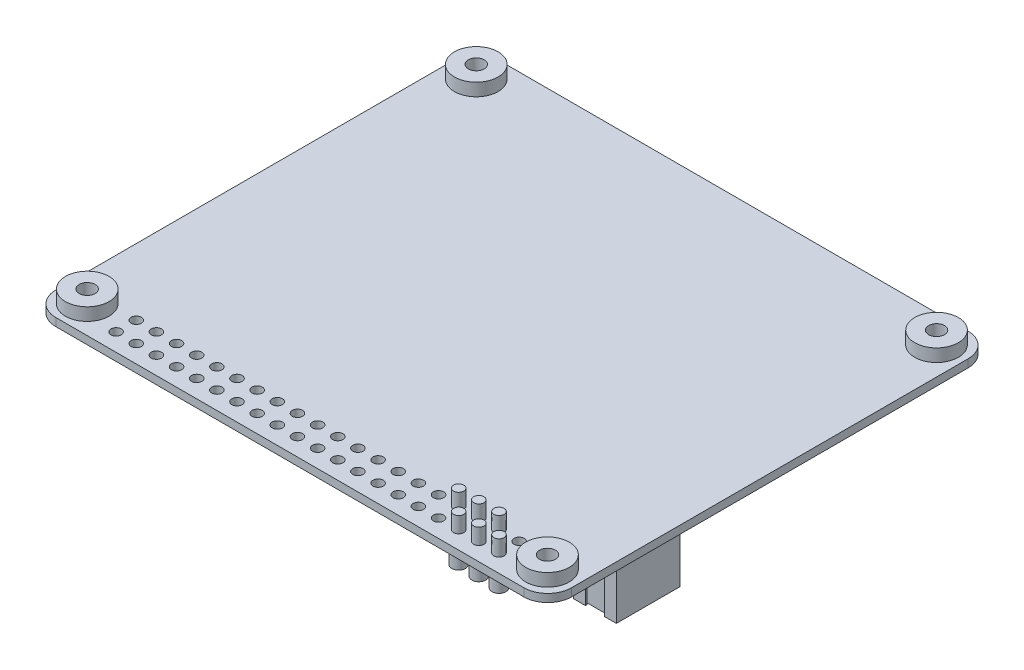
SolidWorks part; units mm, degrees
ref_plane "前视基准面" through (0, 0, 0) normal (0, 0, 1) x (1, 0, 0)
ref_plane "上视基准面" through (0, 0, 0) normal (0, 1, 0) x (1, 0, 0)
ref_plane "右视基准面" through (0, 0, 0) normal (1, 0, 0) x (0, 0, -1)
sketch "草图1" plane through (0, 0, 0) normal (0, 1, 0) x (1, 0, 0)
  line L1 (32.5, -28) -> (-32.5, -28)
  line L2 (32.5, -28) -> (32.5, 28)
  line L3 (32.5, 28) -> (-32.5, 28)
  line L4 (-32.5, -28) -> (-32.5, 28)
  line L5 (32.5, -28) -> (-32.5, 28) construction
  line L6 (32.5, 28) -> (-32.5, -28) construction
  point P0 (0, 0)
  dimension "D1" = 56
  dimension "D2" = 65
extrude "凸台-拉伸1" add sketch "草图1" along normal blind 1
fillet "圆角1" radius 3 4 edges at (32.5, 0.5, -28) (32.5, 0.5, 28) (-32.5, 0.5, 28) (-32.5, 0.5, -28)
sketch "草图2" plane through (0, 1, 0) normal (0, 1, 0) x (1, 0, 0)
  circle A0 centre (-29.0307, 24.5287) radius 2.75
  circle A1 centre (28.9808, 24.5287) radius 2.75
  circle A2 centre (-29.0307, -24.5065) radius 2.75
  circle A3 centre (28.9808, -24.5065) radius 2.75
  dimension "D1" = 5.5
extrude "凸台-拉伸2" add sketch "草图2" along normal blind 1.6
sketch "草图3" plane through (0, 2.6, 0) normal (0, 1, 0) x (1, 0, 0)
  circle A0 centre (-29.0307, 24.5287) radius 1
  circle A1 centre (28.9808, 24.5287) radius 1
  circle A2 centre (-29.0307, -24.5065) radius 1
  circle A3 centre (28.9808, -24.5065) radius 1
  dimension "D1" = 2
extrude "切除-拉伸1" cut sketch "草图3" against normal up to next
sketch "草图4" plane through (0, 0, 0) normal (0, -1, 0) x (1, 0, 0)
  line L0 (29.5, -28) -> (-29.5, -28) construction
  line L1 (25.5, -28) -> (16.5, -28)
  line L2 (25.5, -28) -> (25.5, -20.6)
  line L3 (25.5, -20.6) -> (16.5, -20.6)
  line L4 (16.5, -28) -> (16.5, -20.6)
  line L5 (32.5, 25) -> (32.5, -25) construction
  dimension "D1" = 7.4
  dimension "D2" = 9
  dimension "D3" = 7
extrude "凸台-拉伸3" add sketch "草图4" along normal blind 3.2
sketch "草图5" plane through (0, 0, -28) normal (0, 0, -1) x (-1, 0, 0)
  line L0 (-29.5, 0) -> (-25.5, 0) construction
  line L1 (-16.5, -3.2) -> (-25.5, -3.2)
  line L2 (-16.5, -3.2) -> (-16.5, 0)
  line L3 (-16.5, 0) -> (-25.5, 0)
  line L4 (-25.5, -3.2) -> (-25.5, 0)
  line L5 (-25.5, -3.2) -> (-25.5, 0) construction
extrude "凸台-拉伸4" add sketch "草图5" along normal blind 1
fillet "圆角3" radius 1 4 edges at (25.5, 0, -28.5) (25.5, -3.2, -24.8) (16.5, -3.2, -24.8) (16.5, 0, -28.5)
sketch "草图6" plane through (0, 0, 0) normal (0, -1, 0) x (1, 0, 0)
  line L0 (-32.5, -25) -> (-32.5, 25) construction
  circle A0 centre (-17.5, 0) radius 7
  dimension "D1" = 14
  dimension "D2" = 15
extrude "凸台-拉伸5" add sketch "草图6" along normal blind 2
sketch "草图8" plane through (0, 0, 0) normal (0, -1, 0) x (1, 0, 0)
  circle A0 centre (28.9808, 24.5065) radius 2
  circle A1 centre (28.9808, -24.5287) radius 2
  circle A2 centre (-29.0307, -24.5287) radius 2
  circle A3 centre (-29.0307, 24.5065) radius 2
  dimension "D1" = 4
extrude "凸台-拉伸6" add sketch "草图8" along normal blind 0.5
sketch "草图9" plane through (0, 0, 0) normal (0, 1, 0) x (1, 0, 0)
  circle A0 centre (-29.0307, 24.5287) radius 1
  circle A1 centre (28.9808, 24.5287) radius 1
  circle A2 centre (-29.0307, -24.5065) radius 1
  circle A3 centre (28.9808, -24.5065) radius 1
  circle A4 centre (28.9808, -24.5065) radius 2 construction
  circle A5 centre (28.9808, 24.5287) radius 2 construction
  circle A6 centre (-29.0307, -24.5065) radius 2 construction
  circle A7 centre (-29.0307, 24.5287) radius 2 construction
extrude "切除-拉伸2" cut sketch "草图9" against normal up to next
sketch "草图10" plane through (0, 0, -29) normal (0, 0, -1) x (-1, 0, 0)
  line L8 (-17.5, -0.2) -> (-24.5, -0.2)
  line L9 (-25.3, -1) -> (-25.3, -2.2)
  line L10 (-24.5, -3) -> (-17.5, -3)
  line L11 (-16.7, -2.2) -> (-16.7, -1)
  line L12 (-17.5, -0.2) -> (-24.5, -0.2)
  line L13 (-25.3, -1) -> (-25.3, -2.2)
  line L14 (-24.5, -3) -> (-17.5, -3)
  line L15 (-16.7, -2.2) -> (-16.7, -1)
  arc A8 (-24.5, -0.2) -> (-25.3, -1) centre (-24.5, -1) ccw
  arc A9 (-25.3, -2.2) -> (-24.5, -3) centre (-24.5, -2.2) ccw
  arc A10 (-17.5, -3) -> (-16.7, -2.2) centre (-17.5, -2.2) ccw
  arc A11 (-16.7, -1) -> (-17.5, -0.2) centre (-17.5, -1) ccw
  arc A12 (-24.5, -0.2) -> (-25.3, -1) centre (-24.5, -1) ccw
  arc A13 (-25.3, -2.2) -> (-24.5, -3) centre (-24.5, -2.2) ccw
  arc A14 (-17.5, -3) -> (-16.7, -2.2) centre (-17.5, -2.2) ccw
  arc A15 (-16.7, -1) -> (-17.5, -0.2) centre (-17.5, -1) ccw
  dimension "D1" = 0.2
extrude "切除-拉伸3" cut sketch "草图10" against normal blind 8
sketch "草图11" plane through (0, 0, 0) normal (0, -1, 0) x (1, 0, 0)
  line L0 (16.5, -28) -> (-29.5, -28) construction
  line L1 (6, -27.8) -> (10.5, -27.8)
  line L2 (6, -27.8) -> (6, -26.3)
  line L3 (6, -26.3) -> (10.5, -26.3)
  line L4 (10.5, -27.8) -> (10.5, -26.3)
  line L5 (16.5, -20.6) -> (16.5, -28) construction
  line L6 (-2.6793, -27.2) -> (-9.3793, -27.2)
  line L7 (-2.6793, -27.2) -> (-2.6793, -25)
  line L8 (-2.6793, -25) -> (-9.3793, -25)
  line L9 (-9.3793, -27.2) -> (-9.3793, -25)
  dimension "D1" = 6
  dimension "D2" = 4.5
  dimension "D3" = 6.7
  dimension "D4" = 0.8
  dimension "D5" = 2.2
  dimension "D6" = 1.5
  dimension "D7" = 8.7
  dimension "D8" = 0.2
extrude "凸台-拉伸7" add sketch "草图11" along normal blind 1.5
sketch "草图12" plane through (0, 0, 0) normal (0, -1, 0) x (1, 0, 0)
  line L0 (16.5, -28) -> (-29.5, -28) construction
  line L1 (-16.6, -28) -> (-23.9, -28)
  line L2 (-16.6, -28) -> (-16.6, -22.7)
  line L3 (-16.6, -22.7) -> (-23.9, -22.7)
  line L4 (-23.9, -28) -> (-23.9, -22.7)
  line L5 (-32.5, -25) -> (-32.5, 25) construction
  dimension "D1" = 7.3
  dimension "D2" = 8.6
  dimension "D3" = 5.3
extrude "凸台-拉伸8" add sketch "草图12" along normal blind 2.4
sketch "草图13" plane through (0, 0, -28) normal (0, 0, -1) x (-1, 0, 0)
  line L1 (23.9, -2.4) -> (16.6, -2.4)
  line L2 (23.9, -2.4) -> (23.9, 0)
  line L3 (23.9, 0) -> (16.6, 0)
  line L4 (16.6, -2.4) -> (16.6, 0)
extrude "凸台-拉伸9" add sketch "草图13" along normal up to surface (1 mm away) up to face at (21, -1.6, -29)
chamfer "倒角1" distance 0.4 angle 45 2 edges at (-16.6, -2.4, -25.85) (-23.9, -2.4, -25.85)
chamfer "倒角2" distance 1 angle 45 2 edges at (-16.6, 0, -28.5) (-23.9, 0, -28.5)
sketch "草图14" plane through (0, 0, -29) normal (0, 0, -1) x (-1, 0, 0)
  line L16 (22.8172, -0.2) -> (17.6828, -0.2)
  line L17 (17.6828, -0.2) -> (16.8, -1.0828)
  line L18 (16.8, -1.0828) -> (16.8, -1.9172)
  line L19 (16.8, -1.9172) -> (17.0828, -2.2)
  line L20 (17.0828, -2.2) -> (23.4172, -2.2)
  line L21 (23.4172, -2.2) -> (23.7, -1.9172)
  line L22 (23.7, -1.9172) -> (23.7, -1.0828)
  line L23 (23.7, -1.0828) -> (22.8172, -0.2)
  line L24 (22.8172, -0.2) -> (17.6828, -0.2)
  line L25 (17.6828, -0.2) -> (16.8, -1.0828)
  line L26 (16.8, -1.0828) -> (16.8, -1.9172)
  line L27 (16.8, -1.9172) -> (17.0828, -2.2)
  line L28 (17.0828, -2.2) -> (23.4172, -2.2)
  line L29 (23.4172, -2.2) -> (23.7, -1.9172)
  line L30 (23.7, -1.9172) -> (23.7, -1.0828)
  line L31 (23.7, -1.0828) -> (22.8172, -0.2)
  dimension "D1" = 0.2
extrude "切除-拉伸4" cut sketch "草图14" against normal blind 2.4
sketch "草图15" plane through (0, 0, -27.2) normal (0, 0, -1) x (-1, 0, 0)
  line L1 (6.6577, -1.3336) -> (5.7436, -1.3336)
  line L2 (6.6577, -1.3336) -> (6.6577, -0.2043)
  line L3 (6.6577, -0.2043) -> (5.7436, -0.2043)
  line L4 (5.7436, -1.3336) -> (5.7436, -0.2043)
extrude "凸台-拉伸10" add sketch "草图15" along normal blind 0.8
sketch "草图16" plane through (0, 0, -27.8) normal (0, 0, -1) x (-1, 0, 0)
  line L1 (-6.8432, -1.3088) -> (-8.9595, -1.3088)
  line L2 (-6.8432, -1.3088) -> (-6.8432, -0.1641)
  line L3 (-6.8432, -0.1641) -> (-8.9595, -0.1641)
  line L4 (-8.9595, -1.3088) -> (-8.9595, -0.1641)
extrude "凸台-拉伸11" add sketch "草图16" along normal blind 0.5
sketch "草图17" plane through (0, 0, -28) normal (0, 0, -1) x (-1, 0, 0)
  line L0 (23.9, -1) -> (23.9, 0)
  line L1 (23.9, 0) -> (22.9, 0)
  line L2 (22.9, 0) -> (23.9, -1)
  line L3 (16.6, 0) -> (17.6, 0)
  line L4 (17.6, 0) -> (16.6, -1)
  line L5 (16.6, -1) -> (16.6, 0) construction
  line L6 (16.6, -1) -> (16.6, 0)
extrude "切除-拉伸5" cut sketch "草图17" against normal up to surface (5.3 mm away) up to face at (-20.25, -1.4667, -22.7)
fillet "圆角4" radius 0.2 1 edges at (-17.5, -2, -7)
sketch "草图18" plane through (0, 0, 0) normal (0, -1, 0) x (1, 0, 0)
  line L0 (-29.5, 28) -> (29.5, 28) construction
  line L1 (27.1, 8.3) -> (20.1, 8.3)
  line L2 (27.1, 8.3) -> (27.1, 1.3)
  line L3 (27.1, 1.3) -> (20.1, 1.3)
  line L4 (20.1, 8.3) -> (20.1, 1.3)
  line L5 (27.1, -3.4) -> (20.1, -3.4)
  line L6 (27.1, -3.4) -> (27.1, -10.4)
  line L7 (27.1, -10.4) -> (20.1, -10.4)
  line L8 (20.1, -3.4) -> (20.1, -10.4)
  line L9 (32.5, 25) -> (32.5, -25) construction
  dimension "D1" = 7
  dimension "D2" = 19.7
  dimension "D3" = 4.7
  dimension "D4" = 5.4
extrude "凸台-拉伸12" add sketch "草图18" along normal blind 3
sketch "草图19" plane through (0, 0, 0) normal (0, -1, 0) x (1, 0, 0)
  line L0 (32.5, 25) -> (32.5, -25) construction
  line L1 (32, 18.85) -> (26.6, 18.85)
  line L2 (32, 18.85) -> (32, 10.85)
  line L3 (32, 10.85) -> (26.6, 10.85)
  line L4 (26.6, 18.85) -> (26.6, 10.85)
  line L5 (-29.5, 28) -> (29.5, 28) construction
  dimension "D1" = 8
  dimension "D2" = 5.4
  dimension "D3" = 0.5
  dimension "D4" = 9.15
extrude "凸台-拉伸13" add sketch "草图19" along normal blind 6.22
sketch "草图20" plane through (0, -6.22, 0) normal (0, -1, 0) x (1, 0, 0)
  line L0 (30.5, 18.85) -> (30.5, 18.65)
  line L1 (32, 18.85) -> (26.6, 18.85) construction
  line L2 (30.5, 18.65) -> (31.3599, 18.65)
  line L3 (31.3599, 18.65) -> (31.3599, 18.45)
  line L4 (31.3599, 18.45) -> (26.9378, 18.45)
  line L5 (26.9378, 18.45) -> (26.9378, 18.65)
  line L6 (26.9378, 18.65) -> (28.1, 18.65)
  line L7 (28.1, 18.65) -> (28.1, 18.85)
  line L8 (32, 18.85) -> (26.6, 18.85) construction
  line L9 (28.1, 18.85) -> (30.5, 18.85)
  line L10 (30.5, 10.85) -> (30.5, 11.05)
  line L11 (26.6, 10.85) -> (32, 10.85) construction
  line L12 (30.5, 11.05) -> (31.3599, 11.05)
  line L13 (31.3599, 11.05) -> (31.3599, 11.25)
  line L14 (31.3599, 11.25) -> (26.9378, 11.25)
  line L15 (26.9378, 11.25) -> (26.9378, 11.05)
  line L16 (26.9378, 11.05) -> (28.1, 11.05)
  line L17 (28.1, 11.05) -> (28.1, 10.85)
  line L18 (28.1, 10.85) -> (30.5, 10.85)
  line L19 (32, 10.85) -> (32, 18.85) construction
  line L20 (26.6, 18.85) -> (26.6, 10.85) construction
  dimension "D1" = 0.2
  dimension "D2" = 0.2
  dimension "D3" = 0.2
  dimension "D4" = 1.5
  dimension "D5" = 1.5
extrude "切除-拉伸6" cut sketch "草图20" against normal blind 6.22
sketch "草图21" plane through (0, -6.22, 0) normal (0, -1, 0) x (1, 0, 0)
  line L1 (31.3599, 18.0753) -> (26.9378, 18.0753)
  line L2 (31.3599, 18.0753) -> (31.3599, 11.6247)
  line L3 (31.3599, 11.6247) -> (26.9378, 11.6247)
  line L4 (26.9378, 18.0753) -> (26.9378, 11.6247)
  line L5 (31.3599, 18.0753) -> (26.9378, 11.6247) construction
  line L6 (31.3599, 11.6247) -> (26.9378, 18.0753) construction
  point P0 (29.1489, 14.85)
extrude "切除-拉伸7" cut sketch "草图21" against normal blind 5
sketch "草图22" plane through (0, -1.22, 0) normal (0, -1, 0) x (1, 0, 0)
  line L1 (29.5742, 16.0721) -> (29.0742, 16.0721)
  line L2 (29.5742, 16.0721) -> (29.5742, 15.5721)
  line L3 (29.5742, 15.5721) -> (29.0742, 15.5721)
  line L4 (29.0742, 16.0721) -> (29.0742, 15.5721)
  line L5 (29.5742, 16.0721) -> (29.0742, 15.5721) construction
  line L6 (29.5742, 15.5721) -> (29.0742, 16.0721) construction
  line L7 (29.5566, 14.331) -> (29.0566, 14.331)
  line L8 (29.5566, 14.331) -> (29.5566, 13.831)
  line L9 (29.5566, 13.831) -> (29.0566, 13.831)
  line L10 (29.0566, 14.331) -> (29.0566, 13.831)
  line L11 (29.5566, 14.331) -> (29.0566, 13.831) construction
  line L12 (29.5566, 13.831) -> (29.0566, 14.331) construction
  point P0 (29.3242, 15.8221)
  point P5 (29.3066, 14.081)
  dimension "D1" = 0.5
extrude "凸台-拉伸14" add sketch "草图22" along normal blind 5
chamfer "倒角3" distance 0.1 angle 45 8 edges at (29.3066, -6.22, 14.331) (29.5566, -6.22, 14.081) (29.3066, -6.22, 13.831) (29.0566, -6.22, 14.081) (29.3242, -6.22, 16.0721) (29.5742, -6.22, 15.8221) (29.3242, -6.22, 15.5721) (29.0742, -6.22, 15.8221)
sketch "草图23" plane through (0, 0, 0) normal (0, -1, 0) x (1, 0, 0)
  circle A0 centre (12.8757, -15.76) radius 3.3198
extrude "凸台-拉伸15" add sketch "草图23" along normal blind 1.5
sketch "草图24" plane through (0, 0, 0) normal (0, -1, 0) x (1, 0, 0)
  line L1 (18.7716, 11.9855) -> (16.6907, 11.9855)
  line L2 (18.7716, 11.9855) -> (18.7716, 7.4768)
  line L3 (18.7716, 7.4768) -> (16.6907, 7.4768)
  line L4 (16.6907, 11.9855) -> (16.6907, 7.4768)
  line L5 (18.7716, 11.9855) -> (16.6907, 7.4768) construction
  line L6 (18.7716, 7.4768) -> (16.6907, 11.9855) construction
  line L7 (18.7716, 5.3092) -> (16.6907, 5.3092)
  line L8 (18.7716, 5.3092) -> (18.7716, 0.974)
  line L9 (18.7716, 0.974) -> (16.6907, 0.974)
  line L10 (16.6907, 5.3092) -> (16.6907, 0.974)
  line L11 (18.7716, 5.3092) -> (16.6907, 0.974) construction
  line L12 (18.7716, 0.974) -> (16.6907, 5.3092) construction
  line L13 (15.6772, -1.762) -> (10.6483, -1.762)
  line L14 (15.6772, -1.762) -> (15.6772, -7.762)
  line L15 (15.6772, -7.762) -> (10.6483, -7.762)
  line L16 (10.6483, -1.762) -> (10.6483, -7.762)
  line L17 (15.6772, -1.762) -> (10.6483, -7.762) construction
  line L18 (15.6772, -7.762) -> (10.6483, -1.762) construction
  point P0 (17.7311, 9.7312)
  point P5 (17.7311, 3.1416)
  point P10 (13.1628, -4.762)
  dimension "D1" = 6
extrude "凸台-拉伸16" add sketch "草图24" along normal blind 1.5
sketch "草图25" plane through (0, 0, 0) normal (0, -1, 0) x (1, 0, 0)
  line L1 (15.1967, 7.9079) -> (11.1314, 7.9079)
  line L2 (15.1967, 7.9079) -> (15.1967, 3.8427)
  line L3 (15.1967, 3.8427) -> (11.1314, 3.8427)
  line L4 (11.1314, 7.9079) -> (11.1314, 3.8427)
  line L5 (15.1967, 7.9079) -> (11.1314, 3.8427) construction
  line L6 (15.1967, 3.8427) -> (11.1314, 7.9079) construction
  line L7 (21.5006, 15.4932) -> (19.7006, 15.4932)
  line L8 (21.5006, 15.4932) -> (21.5006, 14.4025)
  line L9 (21.5006, 14.4025) -> (19.7006, 14.4025)
  line L10 (19.7006, 15.4932) -> (19.7006, 14.4025)
  line L11 (21.5006, 15.4932) -> (19.7006, 14.4025) construction
  line L12 (21.5006, 14.4025) -> (19.7006, 15.4932) construction
  line L13 (21.5006, 13.6588) -> (19.7006, 13.6588)
  line L14 (21.5006, 13.6588) -> (21.5006, 12.5682)
  line L15 (21.5006, 12.5682) -> (19.7006, 12.5682)
  line L16 (19.7006, 13.6588) -> (19.7006, 12.5682)
  line L17 (21.5006, 13.6588) -> (19.7006, 12.5682) construction
  line L18 (21.5006, 12.5682) -> (19.7006, 13.6588) construction
  line L19 (21.5006, 11.8741) -> (19.7006, 11.8741)
  line L20 (21.5006, 11.8741) -> (21.5006, 10.7834)
  line L21 (21.5006, 10.7834) -> (19.7006, 10.7834)
  line L22 (19.7006, 11.8741) -> (19.7006, 10.7834)
  line L23 (21.5006, 11.8741) -> (19.7006, 10.7834) construction
  line L24 (21.5006, 10.7834) -> (19.7006, 11.8741) construction
  line L25 (18.7662, 14.8563) -> (17.6756, 14.8563)
  line L26 (18.7662, 14.8563) -> (18.7662, 13.0563)
  line L27 (18.7662, 13.0563) -> (17.6756, 13.0563)
  line L28 (17.6756, 14.8563) -> (17.6756, 13.0563)
  line L29 (18.7662, 14.8563) -> (17.6756, 13.0563) construction
  line L30 (18.7662, 13.0563) -> (17.6756, 14.8563) construction
  line L31 (16.9319, 14.8563) -> (15.8412, 14.8563)
  line L32 (16.9319, 14.8563) -> (16.9319, 13.0563)
  line L33 (16.9319, 13.0563) -> (15.8412, 13.0563)
  line L34 (15.8412, 14.8563) -> (15.8412, 13.0563)
  line L35 (16.9319, 14.8563) -> (15.8412, 13.0563) construction
  line L36 (16.9319, 13.0563) -> (15.8412, 14.8563) construction
  line L37 (15.0976, 14.8563) -> (14.0069, 14.8563)
  line L38 (15.0976, 14.8563) -> (15.0976, 13.0563)
  line L39 (15.0976, 13.0563) -> (14.0069, 13.0563)
  line L40 (14.0069, 14.8563) -> (14.0069, 13.0563)
  line L41 (15.0976, 14.8563) -> (14.0069, 13.0563) construction
  line L42 (15.0976, 13.0563) -> (14.0069, 14.8563) construction
  line L43 (13.2632, 14.8563) -> (12.1725, 14.8563)
  line L44 (13.2632, 14.8563) -> (13.2632, 13.0563)
  line L45 (13.2632, 13.0563) -> (12.1725, 13.0563)
  line L46 (12.1725, 14.8563) -> (12.1725, 13.0563)
  line L47 (13.2632, 14.8563) -> (12.1725, 13.0563) construction
  line L48 (13.2632, 13.0563) -> (12.1725, 14.8563) construction
  line L49 (11.3297, 14.8563) -> (10.2391, 14.8563)
  line L50 (11.3297, 14.8563) -> (11.3297, 13.0563)
  line L51 (11.3297, 13.0563) -> (10.2391, 13.0563)
  line L52 (10.2391, 14.8563) -> (10.2391, 13.0563)
  line L53 (11.3297, 14.8563) -> (10.2391, 13.0563) construction
  line L54 (11.3297, 13.0563) -> (10.2391, 14.8563) construction
  line L55 (9.2971, 14.8563) -> (8.2064, 14.8563)
  line L56 (9.2971, 14.8563) -> (9.2971, 13.0563)
  line L57 (9.2971, 13.0563) -> (8.2064, 13.0563)
  line L58 (8.2064, 14.8563) -> (8.2064, 13.0563)
  line L59 (9.2971, 14.8563) -> (8.2064, 13.0563) construction
  line L60 (9.2971, 13.0563) -> (8.2064, 14.8563) construction
  point P0 (13.1641, 5.8753)
  point P5 (20.6006, 14.9478)
  point P10 (20.6006, 13.1135)
  point P15 (20.6006, 11.3287)
  point P20 (18.2209, 13.9563)
  point P25 (16.3866, 13.9563)
  point P30 (14.5522, 13.9563)
  point P35 (12.7179, 13.9563)
  point P40 (10.7844, 13.9563)
  point P45 (8.7518, 13.9563)
  dimension "D1" = 1.8
extrude "凸台-拉伸17" add sketch "草图25" along normal blind 1
sketch "草图26" plane through (0, 0, 0) normal (0, -1, 0) x (1, 0, 0)
  circle A0 centre (24.13, 25.77) radius 0.65
  circle A40 centre (21.59, 25.77) radius 0.65
  circle A41 centre (19.05, 25.77) radius 0.65
  circle A42 centre (16.51, 25.77) radius 0.65
  circle A43 centre (13.97, 25.77) radius 0.65
  circle A44 centre (11.43, 25.77) radius 0.65
  circle A45 centre (8.89, 25.77) radius 0.65
  circle A46 centre (6.35, 25.77) radius 0.65
  circle A47 centre (3.81, 25.77) radius 0.65
  circle A48 centre (1.27, 25.77) radius 0.65
  circle A49 centre (-1.27, 25.77) radius 0.65
  circle A50 centre (-3.81, 25.77) radius 0.65
  circle A51 centre (-6.35, 25.77) radius 0.65
  circle A52 centre (-8.89, 25.77) radius 0.65
  circle A53 centre (-11.43, 25.77) radius 0.65
  circle A54 centre (-13.97, 25.77) radius 0.65
  circle A55 centre (-16.51, 25.77) radius 0.65
  circle A56 centre (-19.05, 25.77) radius 0.65
  circle A57 centre (-21.59, 25.77) radius 0.65
  circle A58 centre (-24.13, 25.77) radius 0.65
  circle A59 centre (21.59, 23.23) radius 0.65
  circle A60 centre (19.05, 23.23) radius 0.65
  circle A61 centre (16.51, 23.23) radius 0.65
  circle A62 centre (13.97, 23.23) radius 0.65
  circle A63 centre (11.43, 23.23) radius 0.65
  circle A64 centre (8.89, 23.23) radius 0.65
  circle A65 centre (6.35, 23.23) radius 0.65
  circle A66 centre (3.81, 23.23) radius 0.65
  circle A67 centre (1.27, 23.23) radius 0.65
  circle A68 centre (-1.27, 23.23) radius 0.65
  circle A69 centre (-3.81, 23.23) radius 0.65
  circle A70 centre (-6.35, 23.23) radius 0.65
  circle A71 centre (-8.89, 23.23) radius 0.65
  circle A72 centre (-11.43, 23.23) radius 0.65
  circle A73 centre (-13.97, 23.23) radius 0.65
  circle A74 centre (-16.51, 23.23) radius 0.65
  circle A75 centre (-19.05, 23.23) radius 0.65
  circle A76 centre (-21.59, 23.23) radius 0.65
  circle A77 centre (-24.13, 23.23) radius 0.65
  circle A78 centre (24.13, 23.23) radius 0.65
  dimension "D1" = 1.3
  dimension "D2" = 20
  dimension "D3" = 2
extrude "切除-拉伸8" cut sketch "草图26" against normal up to surface (1 mm away) up to face at (28.9808, 1, 27.2565)
sketch "草图27" plane through (0, 0, 0) normal (0, -1, 0) x (1, 0, 0)
  circle A0 centre (24.13, 25.77) radius 1.15
  circle A1 centre (21.59, 25.77) radius 1.15
  circle A2 centre (21.59, 23.23) radius 1.15
  circle A3 centre (19.05, 25.77) radius 1.15
  circle A4 centre (19.05, 23.23) radius 1.15
  circle A5 centre (16.51, 23.23) radius 1.15
  circle A6 centre (21.59, 25.77) radius 0.65 construction
  circle A7 centre (16.51, 23.23) radius 0.65 construction
  dimension "D1" = 2.3
extrude "凸台-拉伸18" add sketch "草图27" along normal blind 0.8
sketch "草图28" plane through (0, -0.8, 0) normal (0, -1, 0) x (-1, 0, 0)
  circle A0 centre (-24.13, -25.77) radius 0.875
  circle A1 centre (-21.59, -25.77) radius 0.875
  circle A2 centre (-19.05, -23.23) radius 0.875
  circle A3 centre (-21.59, -23.23) radius 0.875
  circle A4 centre (-19.05, -25.77) radius 0.875
  circle A5 centre (-16.51, -23.23) radius 0.875
  dimension "D1" = 1.75
extrude "凸台-拉伸19" add sketch "草图28" along normal blind 2
sketch "草图29" plane through (0, 0, 0) normal (0, 1, 0) x (1, 0, 0)
  circle A0 centre (19.05, -23.23) radius 0.65 construction
  circle A1 centre (19.05, -25.77) radius 0.65 construction
  circle A2 centre (21.59, -23.23) radius 0.65 construction
  circle A4 centre (24.13, -25.77) radius 0.65 construction
  circle A6 centre (19.05, -23.23) radius 0.65
  circle A7 centre (19.05, -25.77) radius 0.65
  circle A8 centre (21.59, -23.23) radius 0.65
  circle A9 centre (21.59, -25.77) radius 0.65
  circle A10 centre (24.13, -25.77) radius 0.65
  circle A11 centre (16.51, -23.23) radius 0.65
  circle A12 centre (21.59, -25.77) radius 0.65 construction
  circle A13 centre (16.51, -23.23) radius 0.65 construction
extrude "凸台-拉伸20" add sketch "草图29" along normal blind 3
sketch "草图30" plane through (0, 0, 0) normal (0, -1, 0) x (1, 0, 0)
  line L1 (-0.3871, -24.7121) -> (2.6129, -24.7121)
  line L2 (-0.3871, -24.7121) -> (-0.3871, -27.7121)
  line L3 (-0.3871, -27.7121) -> (2.6129, -27.7121)
  line L4 (2.6129, -24.7121) -> (2.6129, -27.7121)
  line L5 (-0.3871, -24.7121) -> (2.6129, -27.7121) construction
  line L6 (-0.3871, -27.7121) -> (2.6129, -24.7121) construction
  point P0 (1.1129, -26.2121)
  dimension "D1" = 3
  dimension "D2" = 3
extrude "凸台-拉伸21" add sketch "草图30" along normal blind 1
sketch "草图31" plane through (0, -1, 0) normal (0, -1, 0) x (1, 0, 0)
  line L0 (2.6129, -27.7121) -> (2.6129, -24.7121) construction
  line L1 (-0.3871, -27.7121) -> (2.6129, -27.7121) construction
  circle A0 centre (1.1129, -26.2121) radius 1
  point P5 (2.6129, -26.2121)
  point P8 (1.1129, -27.7121)
  dimension "D1" = 2
extrude "凸台-拉伸22" add sketch "草图31" along normal blind 0.6
chamfer "倒角4" distance 0.4 angle 45 4 edges at (2.6129, -0.5, -24.7121) (-0.3871, -0.5, -24.7121) (2.6129, -0.5, -27.7121) (-0.3871, -0.5, -27.7121)
